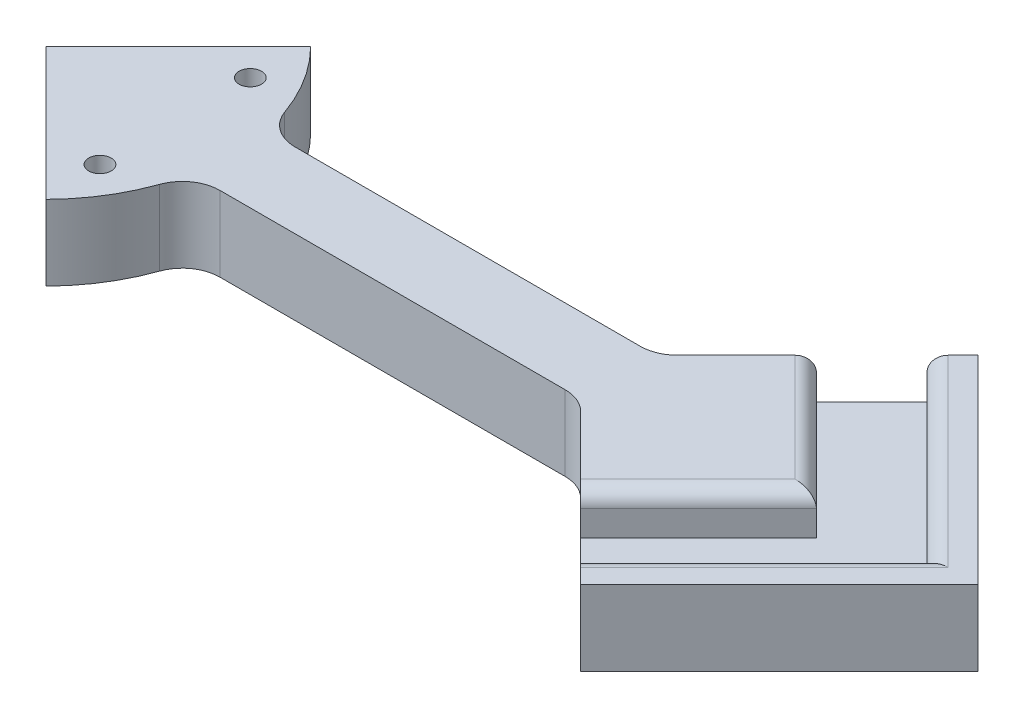
SolidWorks part; units mm, degrees
ref_plane "Front Plane" through (0, 0, 0) normal (0, 0, 1) x (1, 0, 0)
ref_plane "Top Plane" through (0, 0, 0) normal (0, 1, 0) x (1, 0, 0)
ref_plane "Right Plane" through (0, 0, 0) normal (1, 0, 0) x (0, 0, -1)
sketch "Sketch5" plane through (0, 0, 0) normal (0, 1, 0) x (1, 0, 0)
  line L0 (193.4968, 0) -> (0, 0) construction
  line L1 (0, 0) -> (69.85, 69.85) construction
  circle A0 centre (0, 0) radius 162.2828 construction
  circle A1 centre (69.85, 69.85) radius 63.5 construction
  circle A2 centre (69.85, -69.85) radius 63.5 construction
  circle A3 centre (-69.85, -69.85) radius 63.5 construction
  circle A4 centre (-69.85, 69.85) radius 63.5 construction
  point P15 (0, 0)
  dimension "D1" = 324.5656
  dimension "D2" = 127
  dimension "D3" = 45
  dimension "D4" = 4
sketch "Sketch8" plane through (0, 0, 0) normal (0, 0, 1) x (1, 0, 0)
  line L0 (0, 34.2637) -> (0, -61.9336) construction
sketch "Sketch11" plane through (0, 0, 0) normal (0, 1, 0) x (1, 0, 0)
  line L0 (0, 137.9723) -> (0, -128.7054) construction
  line L1 (-137.9723, 0) -> (137.9723, 0) construction
  line L2 (0, 0) -> (88.3597, 88.3597) construction
  dimension "D1" = 45
sketch "Sketch12" plane through (0, 0, 0) normal (0, 1, 0) x (1, 0, 0)
  line L0 (193.4968, 0) -> (0, 0) construction
  line L3 (139.8796, 6.35) -> (6.5296, 6.35)
  line L4 (6.5296, 6.35) -> (0.1796, 0)
  line L5 (0.1796, 0) -> (6.5296, -6.35)
  line L6 (6.5296, -6.35) -> (139.8796, -6.35)
  line L7 (139.8796, -6.35) -> (139.8796, 6.35)
  line L8 (0, 0) -> (69.85, 69.85) construction
  circle A28 centre (69.85, 69.85) radius 63.5 construction
  circle A33 centre (69.85, -69.85) radius 63.5 construction
  point P11 (0, 0)
  point P13 (0, 0)
  point P14 (0, 0)
  point P16 (0, 0)
  point P19 (0, 0)
  point P20 (0, 0)
  dimension "D2" = 4
  dimension "D1" = 0.127
  dimension "D5" = 133.35
extrude "Boss-Extrude11" add sketch "Sketch12" along normal blind 12.7
sketch "Sketch23" plane through (0, 0, 0) normal (0, 1, 0) x (1, 0, 0)
  line L0 (69.85, 69.85) -> (139.7, 0) construction
  line L1 (193.4968, 0) -> (0, 0) construction
  line L2 (90.521, 0) -> (124.0907, 33.5698)
  line L3 (157.6605, 0) -> (124.0907, -33.5698)
  line L4 (124.0907, -33.5698) -> (90.521, 0)
  line L5 (124.0907, 33.5698) -> (157.6605, 0)
  line L7 (0, 0) -> (69.85, 69.85) construction
  dimension "D1" = 12.7
  dimension "D2" = 64.008
extrude "Boss-Extrude12" add sketch "Sketch23" along normal up to surface (12.7 mm away) up to face at (58.5996, 12.7, 0)
sketch "Sketch26" plane through (0, 0, 0) normal (0, 1, 0) x (1, 0, 0)
  line L0 (22.5403, 22.3607) -> (0.1796, 0)
  line L1 (193.4968, 0) -> (0, 0) construction
  line L2 (0.1796, 0) -> (22.5403, -22.3607)
  line L3 (0, 0) -> (69.85, 69.85) construction
  line L4 (6.5296, 6.35) -> (0.1796, 0) construction
  arc A0 (22.5403, -22.3607) -> (22.5403, 22.3607) centre (0, 0) ccw
  dimension "D1" = 63.5
extrude "Boss-Extrude13" add sketch "Sketch26" along normal up to surface (12.7 mm away) up to face at (76.6028, 12.7, 0)
sketch "Sketch24" plane through (0, 0, 0) normal (0, 1, 0) x (1, 0, 0)
  line L0 (119.7802, 29.2592) -> (149.0395, 0)
  line L1 (124.0907, 33.5698) -> (96.871, 6.35) construction
  line L2 (193.4968, 0) -> (0, 0) construction
  line L3 (149.0395, 0) -> (119.7802, -29.2592)
  line L4 (96.871, -6.35) -> (124.0907, -33.5698) construction
  line L5 (119.7802, -29.2592) -> (110.4408, -19.9198)
  line L6 (110.4408, -19.9198) -> (130.3605, 0)
  line L7 (130.3605, 0) -> (110.4408, 19.9198)
  line L8 (110.4408, 19.9198) -> (119.7802, 29.2592)
  line L11 (115.1105, 24.5895) -> (144.3697, -4.6697) construction
  line L12 (157.6605, 0) -> (124.0907, 33.5698) construction
  dimension "D1" = 12.7
  dimension "D2" = 13.208
extrude "Cut-Extrude1" cut sketch "Sketch24" against normal blind 6.858 from surface starting at face at (70.9399, 12.7, 0)
sketch "Sketch25" plane through (0, 0, 0) normal (0, 1, 0) x (1, 0, 0)
  line L0 (193.4968, 0) -> (0, 0) construction
  line L1 (0, 0) -> (21.997, 12.7) construction
  line L2 (0, 0) -> (58.3902, 0) construction
  circle A1 centre (21.997, 12.7) radius 1.9
  circle A2 centre (21.997, -12.7) radius 1.9
  dimension "D1" = 3.8
  dimension "D4" = 25.4
  dimension "D5" = 30
extrude "Cut-Extrude2" cut sketch "Sketch25" along normal through all
fillet "Fillet1" radius 2.54 4 edges at (134.4098, 12.7, 14.6296) (134.4098, 12.7, -14.6296) (120.4006, 12.7, -9.9599) (120.4006, 12.7, 9.9599)
fillet "Fillet2" radius 6.35 4 edges at (96.871, 6.35, -6.35) (96.871, 6.35, 6.35) (31.1085, 6.35, -6.35) (31.1085, 6.35, 6.35)
equation "\"cage spacing\"= 0.5'space between cages"
equation "\"cage diameter\"= 5'cage diameter"
equation "\"cage radius\"= \"cage diameter\" / 2'cage radius"
equation "\"D1@Sketch5\"=2*(2^0.5*(\"cage radius\"+\"cage spacing\"/2)+\"cage radius\")"
equation "\"tightTol\" = 0.005in"
equation "\"normTol\"= 0.01in"
equation "\"looseTol\"= 0.02in"
equation "\"D2@Sketch5\"=\"cage diameter\""
equation "\"D2@Sketch23\"=\"cage radius\"+\"looseTol\""
equation "\"D2@Sketch24\"=\"looseTol\"+0.5"
equation "\"D1@Cut-Extrude1\"=\"looseTol\"+0.25"
equation "\"D1@Sketch25\"=3.8mm"
